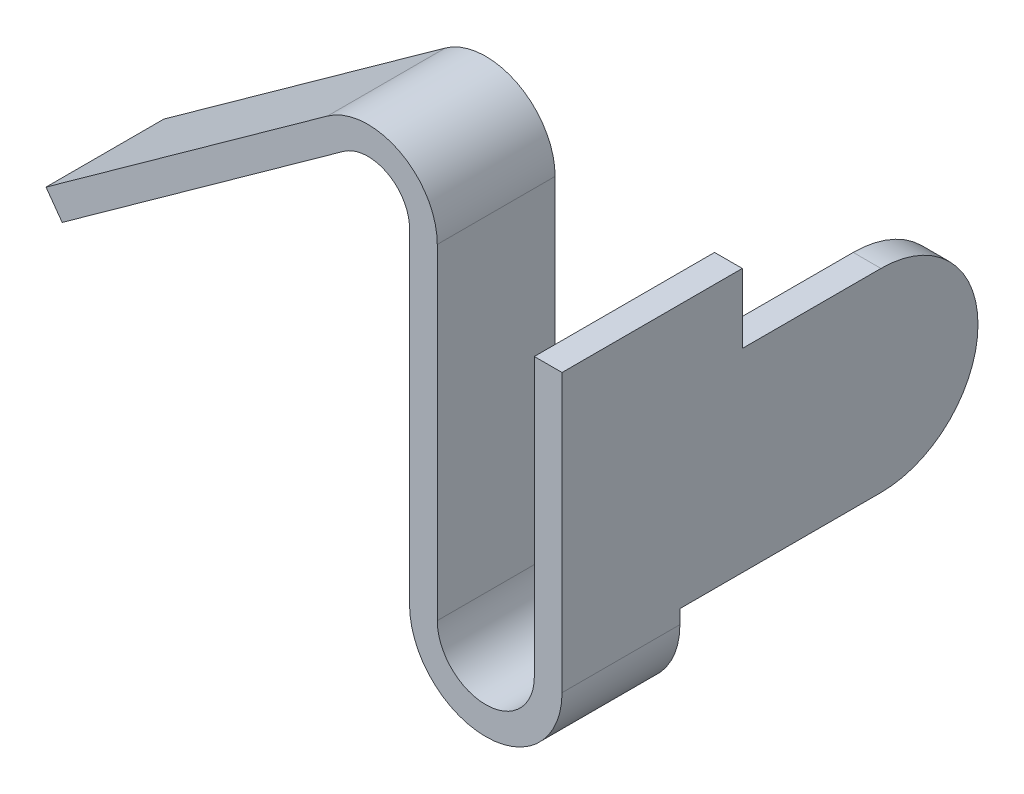
SolidWorks part; units mm, degrees
material "Copper"
ref_plane "Front Plane" through (0, 0, 0) normal (0, 0, 1) x (1, 0, 0)
ref_plane "Top Plane" through (0, 0, 0) normal (0, 1, 0) x (1, 0, 0)
ref_plane "Right Plane" through (0, 0, 0) normal (1, 0, 0) x (0, 0, -1)
sketch "Sketch1" plane through (0, 0, 0) normal (0, 0, 1) x (1, 0, 0)
  line L0 (2.15, -0.8) -> (2.15, 1.2) construction
  line L1 (-1.0219, 0.497) -> (1.0082, 1.956)
  line L2 (1.8, -0.8) -> (1.8, 1.2) construction
  line L3 (2.5, -0.8) -> (2.5, 1.2) construction
  line L4 (2.5, 0.7) -> (2.7, 0.7)
  line L5 (2.5, 0.7) -> (2.5, -0.7) construction
  line L6 (2.5, -0.7) -> (2.7, -0.7)
  line L7 (2.7, 0.7) -> (2.7, -0.7)
  line L8 (2.5, 0.7) -> (2.7, -0.7) construction
  line L9 (2.5, -0.7) -> (2.7, 0.7) construction
  line L10 (1.8, 1.55) -> (1.8, -0.8)
  line L11 (2.5, -0.8) -> (2.5, 1.2)
  line L12 (-0.9052, 0.3346) -> (1.1249, 1.7936)
  line L13 (1.6, 1.55) -> (1.6, -0.8)
  line L14 (2.7, -0.8) -> (2.7, 1.2)
  line L15 (-0.9052, 0.3346) -> (1.1249, 1.7936) construction
  line L16 (-1.0219, 0.497) -> (-0.9052, 0.3346)
  line L17 (2.5, 1.2) -> (2.7, 1.2)
  arc A0 (1.8, -0.8) -> (2.5, -0.8) centre (2.15, -0.8) ccw construction
  arc A1 (2.5, 1.2) -> (1.8, 1.2) centre (2.15, 1.2) ccw construction
  circle A2 centre (0, 0) radius 0.8 construction
  arc A3 (1.0082, 1.956) -> (1.8, 1.55) centre (1.3, 1.55) cw
  arc A4 (1.8, -0.8) -> (2.5, -0.8) centre (2.15, -0.8) ccw
  arc A5 (1.1249, 1.7936) -> (1.6, 1.55) centre (1.3, 1.55) cw
  arc A6 (1.6, -0.8) -> (2.7, -0.8) centre (2.15, -0.8) ccw
  point P4 (2.15, 0.2)
  point P14 (2.6, 0)
  point P28 (2.15, 1.55)
  dimension "D7" = 1.6
  dimension "D8" = 0.5
  dimension "D1" = 2
  dimension "D2" = 0.2
  dimension "D3" = 1.4
  dimension "D4" = 0.7
  dimension "D5" = 0.2
  dimension "D6" = 2.6
  dimension "D9" = 2.5
  dimension "D10" = 0.2
extrude "Boss-Extrude1" add sketch "Sketch1" along normal blind 0.6 contours L13 A6 L14 L6 L11 A4 L10 A3 L1 L16 L12 A5 | L11 L6 L7 L4 | L17 L11 L4 L14 region at (0.0226, 1.1856, 0) region at (2.6, 0, 0) region at (2.6, 0.95, 0)
extrude "Boss-Extrude2" add sketch "Sketch1<3>" against normal blind 0.7 contours L11 L6 L7 L4 | L17 L11 L4 L14 region at (2.6, 0, 0) region at (2.6, 0.95, 0)
sketch "Sketch1<3>" plane through (0, 0, 0) normal (0, 0, 1) x (1, 0, 0) same geometry as "Sketch1"
extrude "Boss-Extrude3" add sketch "Sketch1<5>" against normal blind 1.7 from surface contours L11 L6 L7 L4 region at (2.6, 0, 0) starting at face at (2.6, 0.25, -0.7)
sketch "Sketch1<5>" plane through (0, 0, 0) normal (0, 0, 1) x (1, 0, 0) same geometry as "Sketch1"
fillet "Fillet1" radius 0.7 2 edges at (2.6, 0.7, -2.4) (2.6, -0.7, -2.4)
extrude "Boss-Extrude4" add sketch "Sketch1<6>" against normal blind 0.25 contours L13 A6 L14 L6 L11 A4 L10 A3 L1 L16 L12 A5 region at (0.0226, 1.1856, 0)
sketch "Sketch1<6>" plane through (0, 0, 0) normal (0, 0, 1) x (1, 0, 0) same geometry as "Sketch1"
sketch "Sketch2" plane through (0, -0.7, 0) normal (0, -1, 0) x (1, 0, 0)
  line L0 (2.5, -1.7) -> (2.7, -1.7) construction
  line L1 (2.5, -1.7) -> (2.7, -1.7) construction
  line L2 (2.6, -1.7) -> (2.6, -1.5792) construction
sketch "Sketch3" plane through (0, 0.7, 0) normal (0, 1, 0) x (1, 0, 0)
  line L0 (2.6, 1.7) -> (2.6, 1.5792) construction
  line L1 (2.5, 1.7) -> (2.7, 1.7) construction
  line L2 (2.6, 1.7) -> (2.6, 1.5792) construction
  line L3 (2.5, 1.7) -> (2.7, 1.7) construction
